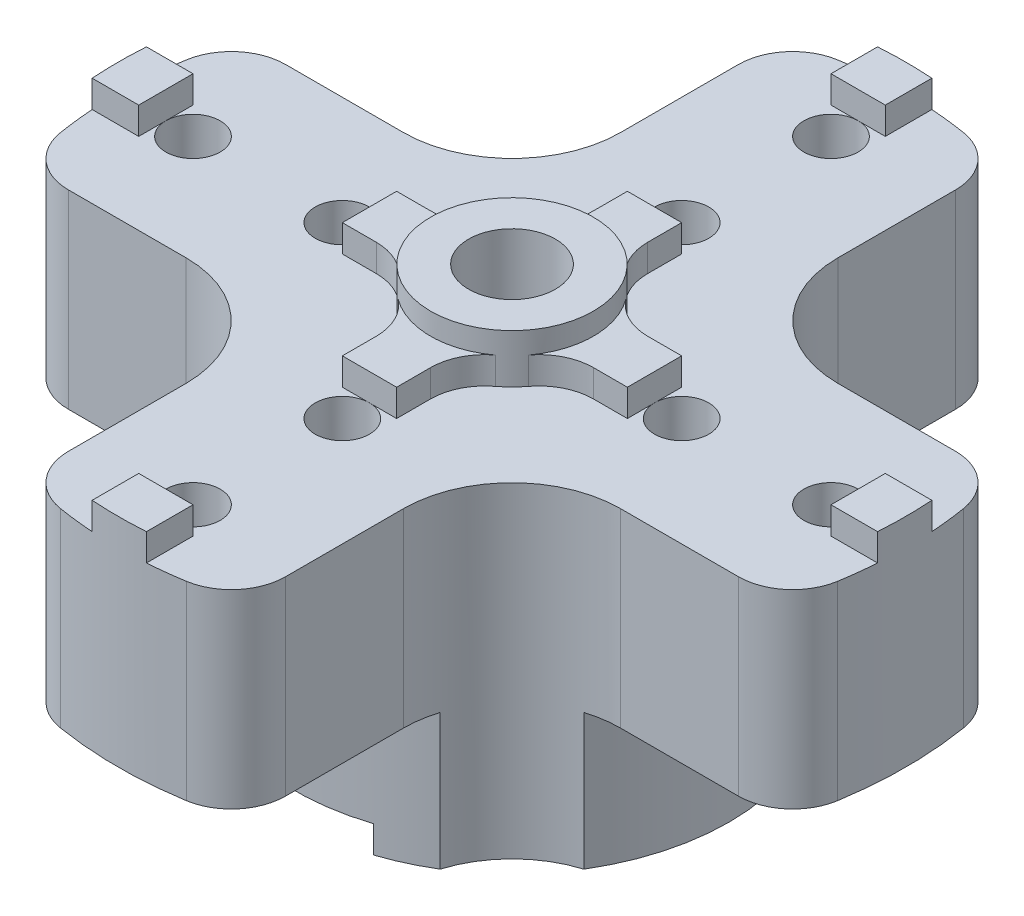
SolidWorks part; units mm, degrees
material "6061-T6 (SS)"
ref_plane "Front Plane" through (0, 0, 0) normal (0, 0, 1) x (1, 0, 0)
ref_plane "Top Plane" through (0, 0, 0) normal (0, 1, 0) x (1, 0, 0)
ref_plane "Right Plane" through (0, 0, 0) normal (1, 0, 0) x (0, 0, -1)
sketch "Sketch3" plane through (0, 0, 0) normal (0, 1, 0) x (1, 0, 0)
  line L0 (-2, -6.9687) -> (-2, -2)
  line L1 (-2, -2) -> (-6.9687, -2)
  line L2 (0, 0) -> (-7.25, 0) construction
  line L3 (0, 0) -> (0, -7.25) construction
  line L4 (0, 0) -> (-6.364, -6.364) construction
  line L5 (-6.9687, 2) -> (-2, 2)
  line L6 (-2, 2) -> (-2, 6.9687)
  line L7 (2, 6.9687) -> (2, 2)
  line L8 (2, 2) -> (6.9687, 2)
  line L9 (6.9687, -2) -> (2, -2)
  line L10 (2, -2) -> (2, -6.9687)
  arc A1 (-7.25, 0) -> (-6.9687, -2) centre (0, 0) ccw
  arc A2 (-2, -6.9687) -> (0, -7.25) centre (0, 0) ccw
  arc A3 (-6.9687, 2) -> (-7.25, 0) centre (0, 0) ccw
  arc A4 (0, 7.25) -> (-2, 6.9687) centre (0, 0) ccw
  arc A5 (2, 6.9687) -> (0, 7.25) centre (0, 0) ccw
  arc A6 (7.25, 0) -> (6.9687, 2) centre (0, 0) ccw
  arc A7 (6.9687, -2) -> (7.25, 0) centre (0, 0) ccw
  arc A8 (0, -7.25) -> (2, -6.9687) centre (0, 0) ccw
  point P29 (0, 0)
  dimension "D4" = 7.25
  dimension "D1" = 45
  dimension "D2" = 4
  dimension "D3" = 4
extrude "Boss-Extrude1" add sketch "Sketch3" along normal blind 3.5
sketch "Sketch4" plane through (0, 3.5, 0) normal (0, 1, 0) x (-1, 0, 0)
  line L0 (0, 0) -> (0, 7.25) construction
  line L1 (-2, 4.5) -> (2, 4.5) construction
  line L3 (2, 2) -> (2, 6.9687) construction
  line L4 (-0.5, 5.875) -> (-0.5, 7.2327)
  line L5 (0.5, 5.875) -> (0.5, 7.2327)
  line L6 (0.5, 3.125) -> (0.5, 0.5)
  line L7 (-0.5, 3.125) -> (-0.5, 0.5)
  line L8 (0, 0) -> (6.364, 6.364) construction
  line L9 (0, 0) -> (-6.364, 6.364) construction
  line L10 (5.875, 0.5) -> (7.2327, 0.5)
  line L11 (5.875, -0.5) -> (7.2327, -0.5)
  line L12 (0.5, -5.875) -> (0.5, -7.2327)
  line L13 (-0.5, -5.875) -> (-0.5, -7.2327)
  line L14 (-5.875, -0.5) -> (-7.2327, -0.5)
  line L15 (-5.875, 0.5) -> (-7.2327, 0.5)
  line L16 (3.125, 0.5) -> (0.5, 0.5)
  line L17 (3.125, -0.5) -> (0.5, -0.5)
  line L18 (0.5, -3.125) -> (0.5, -0.5)
  line L19 (-0.5, -3.125) -> (-0.5, -0.5)
  line L20 (-3.125, -0.5) -> (-0.5, -0.5)
  line L21 (-3.125, 0.5) -> (-0.5, 0.5)
  line L22 (-2, 6.9687) -> (-2, 2) construction
  arc A0 (2, 6.9687) -> (-2, 6.9687) centre (0, 0) ccw construction
  arc A1 (-0.5, 5.875) -> (0.5, 5.875) centre (0, 5.875) ccw
  arc A2 (7.2327, -0.5) -> (7.2327, 0.5) centre (0, 0) ccw
  arc A4 (-0.5, 3.125) -> (0.5, 3.125) centre (0, 3.125) cw
  arc A5 (0.5, 7.2327) -> (-0.5, 7.2327) centre (0, 0) ccw
  arc A7 (5.875, 0.5) -> (5.875, -0.5) centre (5.875, 0) ccw
  arc A8 (-0.5, -7.2327) -> (0.5, -7.2327) centre (0, 0) ccw
  arc A9 (0.5, -5.875) -> (-0.5, -5.875) centre (0, -5.875) ccw
  arc A10 (-7.2327, 0.5) -> (-7.2327, -0.5) centre (0, 0) ccw
  arc A11 (-5.875, -0.5) -> (-5.875, 0.5) centre (-5.875, 0) ccw
  arc A12 (3.125, 0.5) -> (3.125, -0.5) centre (3.125, 0) cw
  arc A13 (0.5, -3.125) -> (-0.5, -3.125) centre (0, -3.125) cw
  arc A14 (-3.125, -0.5) -> (-3.125, 0.5) centre (-3.125, 0) cw
  point P47 (0, 0)
  point P63 (0, 0)
  point P70 (0, 0)
  dimension "D3" = 4
  dimension "D4" = 1
  dimension "D1" = 4.5
  dimension "D2" = 1.375
  dimension "D5" = 0
  dimension "D6" = 45
  dimension "D7" = 45
extrude "Boss-Extrude2" add sketch "Sketch4" along normal blind 0.5
sketch "Sketch5" plane through (0, 4, 0) normal (0, 1, 0) x (-1, 0, 0)
  circle A0 centre (0, 5.875) radius 0.5
  circle A1 centre (0, 3.125) radius 0.5
  arc A2 (0.5, 3.125) -> (-0.5, 3.125) centre (0, 3.125) ccw construction
  arc A3 (-0.5, 5.875) -> (0.5, 5.875) centre (0, 5.875) ccw construction
  circle A4 centre (5.875, 0) radius 0.5
  circle A5 centre (3.125, 0) radius 0.5
  circle A6 centre (0, -5.875) radius 0.5
  circle A7 centre (0, -3.125) radius 0.5
  circle A8 centre (-5.875, 0) radius 0.5
  circle A9 centre (-3.125, 0) radius 0.5
  point P27 (0, 0)
sketch "Sketch6" plane through (0, 0, 0) normal (0, -1, 0) x (1, 0, 0)
  circle A0 centre (0, 0) radius 4
  dimension "D1" = 8
extrude "Boss-Extrude4" add sketch "Sketch6" along normal blind 2
fillet "Fillet1" radius 1 8 edges at (2, 1.75, 6.9687) (6.9687, 1.75, 2) (-2, 1.75, 6.9687) (-6.9687, 1.75, 2) (6.9687, 1.75, -2) (2, 1.75, -6.9687) (-2, 1.75, -6.9687) (-6.9687, 1.75, -2)
sketch "Sketch13" plane through (0, 3.5, 0) normal (0, 1, 0) x (1, 0, 0)
  circle A0 centre (0, 0) radius 1.5
  dimension "D1" = 3
extrude "Boss-Extrude7" add sketch "Sketch13" along normal blind 0.9
hole_wizard "M2x0.4 Tapped Hole1" positions "Sketch8" profile "Sketch7" tap size "M2x0.4" standard "ANSI Metric" end condition through all
sketch "Sketch8" plane through (0, -2, 0) normal (0, -1, 0) x (-1, 0, 0)
  point P0 (0, 0)
cosmetic thread "Hole Thread1" parameters "D2"=2
sketch "Sketch7" plane through (0, -2, 0) normal (1, 0, 0) x (0, 0, -1)
  line L0 (0, 0) -> (0, 6.4)
  line L1 (0, 6.4) -> (0.8, 6.4)
  line L2 (0.8, 6.4) -> (0.8, 0)
  line L5 (0.8, 0) -> (0, 0)
  line L11 (0, -6.35) -> (0, 107.95) construction
  dimension "Thru Tap Drill Dia." = 1.6
  dimension "Thru Tap Drill Depth" = 6.4
sketch "Sketch9" plane through (0, -2, 0) normal (0, -1, 0) x (1, 0, 0)
  line L2 (-1.25, -2.7272) -> (-1.25, -3.7997)
  line L4 (-1.25, 2.7272) -> (-1.25, 3.7997)
  line L6 (0, 0) -> (0, -3.7695) construction
  line L7 (1.25, 2.7272) -> (1.25, 3.7997)
  line L8 (1.25, -2.7272) -> (1.25, -3.7997)
  circle A1 centre (0, 0) radius 4 construction
  arc A2 (1.25, 3.7997) -> (1.25, -3.7997) centre (0, 0) cw
  arc A3 (1.25, 2.7272) -> (1.25, -2.7272) centre (0, 0) cw
  arc A4 (-1.25, 2.7272) -> (-1.25, -2.7272) centre (0, 0) ccw
  arc A5 (-1.25, 3.7997) -> (-1.25, -3.7997) centre (0, 0) ccw
  point P31 (0, 0)
  dimension "D3" = 3
  dimension "D1" = 2.5
  dimension "D2" = 2.5
extrude "Boss-Extrude5" add sketch "Sketch9" along normal blind 0.5
extrude "Cut-Extrude1" cut sketch "Sketch5" against normal blind 3
sketch "Sketch10" plane through (0, 4, 0) normal (0, 1, 0) x (1, 0, 0)
  line L0 (-0.5, -5.875) -> (-0.5, -7.2327) construction
  line L1 (-0.5, -6.375) -> (0.5, -6.375)
  line L2 (-0.5, -6.375) -> (-0.5, -2.625)
  line L3 (-0.5, -2.625) -> (0.5, -2.625)
  line L4 (0.5, -6.375) -> (0.5, -2.625)
  line L5 (0.5, -7.2327) -> (0.5, -5.875) construction
  line L6 (-6.375, 0.5) -> (-2.625, 0.5)
  line L7 (-6.375, 0.5) -> (-6.375, -0.5)
  line L8 (-6.375, -0.5) -> (-2.625, -0.5)
  line L9 (-2.625, 0.5) -> (-2.625, -0.5)
  line L10 (0.5, 6.375) -> (0.5, 2.625)
  line L11 (0.5, 6.375) -> (-0.5, 6.375)
  line L12 (-0.5, 6.375) -> (-0.5, 2.625)
  line L13 (0.5, 2.625) -> (-0.5, 2.625)
  line L14 (6.375, -0.5) -> (2.625, -0.5)
  line L15 (6.375, -0.5) -> (6.375, 0.5)
  line L16 (6.375, 0.5) -> (2.625, 0.5)
  line L17 (2.625, -0.5) -> (2.625, 0.5)
  arc A0 (-0.5, -5.875) -> (0.5, -5.875) centre (0, -5.875) ccw construction
  arc A1 (0.5, -3.125) -> (-0.5, -3.125) centre (0, -3.125) ccw construction
  point P29 (0, 0)
  dimension "D1" = 4
extrude "Cut-Extrude2" cut sketch "Sketch10" against normal up to surface (0.5 mm away) up to face at (0, 3.5, 0)
chamfer "Chamfer1" distance 0.75 angle 45 1 edges at (0, -2, -0.8)
fillet "Fillet2" radius 2 4 edges at (-2, 1.75, -2) (2, 1.75, -2) (2, 1.75, 2) (-2, 1.75, 2)
sketch "Sketch11" plane through (0, 0, 0) normal (0, 1, 0) x (1, 0, 0)
  arc A0 (3.4114, -2.0886) -> (2.0886, -3.4114) centre (4, -4) ccw construction
  arc A1 (2.0886, 3.4114) -> (3.4114, 2.0886) centre (4, 4) ccw construction
  arc A2 (-3.4114, 2.0886) -> (-2.0886, 3.4114) centre (-4, 4) ccw construction
  arc A3 (-2.0886, -3.4114) -> (-3.4114, -2.0886) centre (-4, -4) ccw construction
  arc A4 (-3.4114, -2.0886) -> (-2.0886, -3.4114) centre (0, 0) ccw construction
  arc A5 (2.0886, -3.4114) -> (3.4114, -2.0886) centre (0, 0) ccw construction
  arc A6 (3.4114, 2.0886) -> (2.0886, 3.4114) centre (0, 0) ccw construction
  arc A7 (-2.0886, 3.4114) -> (-3.4114, 2.0886) centre (0, 0) ccw construction
  arc A8 (3.4114, -2.0886) -> (2.0886, -3.4114) centre (4, -4) ccw
  arc A9 (2.0886, 3.4114) -> (3.4114, 2.0886) centre (4, 4) ccw
  arc A10 (-3.4114, 2.0886) -> (-2.0886, 3.4114) centre (-4, 4) ccw
  arc A11 (-2.0886, -3.4114) -> (-3.4114, -2.0886) centre (-4, -4) ccw
  arc A12 (-3.4114, -2.0886) -> (-2.0886, -3.4114) centre (0, 0) ccw
  arc A13 (2.0886, -3.4114) -> (3.4114, -2.0886) centre (0, 0) ccw
  arc A14 (3.4114, 2.0886) -> (2.0886, 3.4114) centre (0, 0) ccw
  arc A15 (-2.0886, 3.4114) -> (-3.4114, 2.0886) centre (0, 0) ccw
extrude "Cut-Extrude3" cut sketch "Sketch11" against normal up to next
fillet "Fillet3" radius 1 8 edges at (-1.4142, 3.75, 0.5) (-0.5, 3.75, 1.4142) (0.5, 3.75, 1.4142) (1.4142, 3.75, 0.5) (1.4142, 3.75, -0.5) (0.5, 3.75, -1.4142) (-0.5, 3.75, -1.4142) (-1.4142, 3.75, -0.5)
